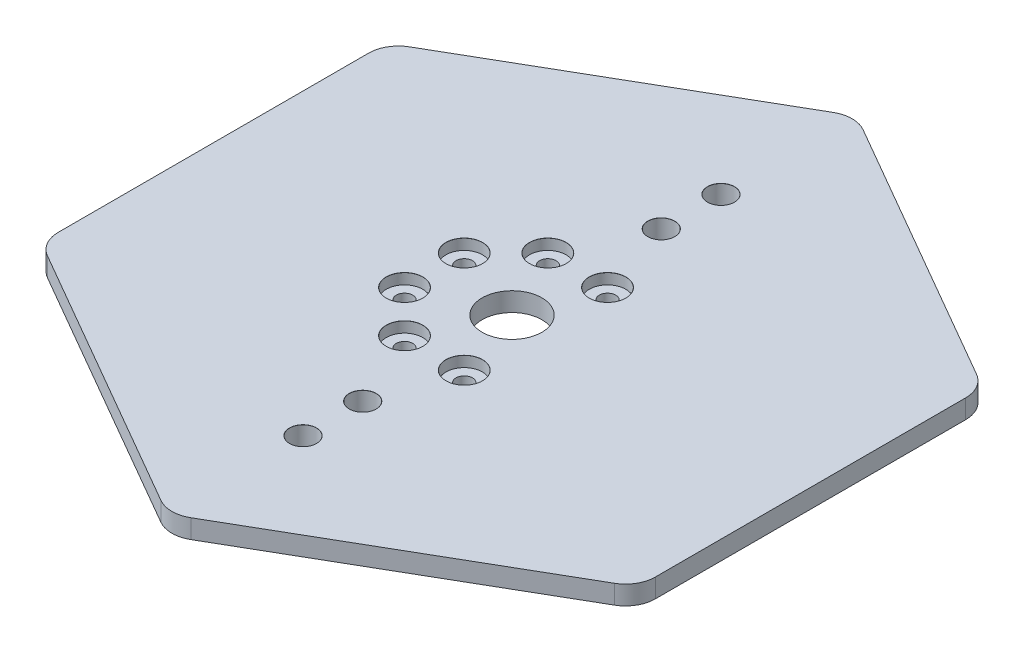
SolidWorks part; units mm, degrees
material "1060 Alloy"
ref_plane "Front Plane" through (0, 0, 0) normal (0, 0, 1) x (1, 0, 0)
ref_plane "Top Plane" through (0, 0, 0) normal (0, 1, 0) x (1, 0, 0)
ref_plane "Right Plane" through (0, 0, 0) normal (1, 0, 0) x (0, 0, -1)
sketch "Sketch1" plane through (0, 0, 0) normal (0, 1, 0) x (1, 0, 0)
  line L1 (100, 57.735) -> (0, 115.4701)
  line L2 (0, 115.4701) -> (-100, 57.735)
  line L3 (-100, 57.735) -> (-100, -57.735)
  line L4 (-100, -57.735) -> (0, -115.4701)
  line L5 (0, -115.4701) -> (100, -57.735)
  line L6 (100, -57.735) -> (100, 57.735)
  circle A0 centre (0, 0) radius 100 construction
  circle A1 centre (0, 0) radius 100 construction
  dimension "D1" = 200
extrude "Boss-Extrude1" add sketch "Sketch1" along normal blind 6.35
sketch "Sketch2" plane through (0, 6.35, 0) normal (0, 1, 0) x (1, 0, 0)
  circle A0 centre (0, 0) radius 10
  dimension "D1" = 20
extrude "Cut-Extrude1" cut sketch "Sketch2" against normal through all
sketch "Sketch3" plane through (0, 6.35, 0) normal (0, 1, 0) x (1, 0, 0)
  line L0 (0, -70) -> (0, 70) construction
  point P3 (0, 0)
  point P4 (0, -50)
  point P6 (0, 50)
  dimension "D1" = 140
  dimension "D2" = 20
  dimension "D3" = 20
hole_wizard "M8 Clearance Hole1" positions "Sketch4" profile "Sketch5" hole size "M8" standard "ANSI Metric" end condition through all
sketch "Sketch4" plane through (0, 6.35, 0) normal (0, 1, 0) x (1, 0, 0)
  point P0 (0, 70)
  point P3 (0, 50)
  point P6 (0, -50)
  point P9 (0, -70)
sketch "Sketch5" plane through (0, 6.35, -70) normal (1, 0, 0) x (0, 0, 1)
  line L0 (0, 0) -> (0, 6.35)
  line L1 (0, 6.35) -> (4.5, 6.35)
  line L2 (4.5, 6.35) -> (4.5, 0.025)
  line L3 (4.5, 0.025) -> (4.525, 0)
  line L5 (4.525, 0) -> (0, 0)
  line L6 (-4.5, 0.025) -> (-4.525, 0) construction
  line L11 (0, -6.35) -> (0, 107.95) construction
  dimension "Thru Hole Dia." = 9
  dimension "Thru Hole Depth" = 6.35
  dimension "Near C'Sink Dia." = 9.05
  dimension "Near C'Sink Angle" = 90
sketch "Sketch6" plane through (0, 6.35, 0) normal (0, 1, 0) x (1, 0, 0)
  line L0 (-55, 0) -> (55, 0) construction
  point P0 (-26, 10)
  point P1 (-12, 24)
  point P2 (8, 24)
  point P3 (8, 24)
  point P12 (8, -24)
  point P13 (-12, -24)
  point P14 (-26, -10)
  dimension "D1" = 8
  dimension "D2" = 24
  dimension "D3" = 26
  dimension "D4" = 20
  dimension "D5" = 10
hole_wizard "CBORE for M5 Hex Head Bolt1" positions "Sketch7" profile "Sketch8" counterbore size "M5" standard "ANSI Metric" end condition through all
sketch "Sketch7" plane through (0, 6.35, 0) normal (0, 1, 0) x (1, 0, 0)
  point P0 (-26, 10)
  point P3 (-12, 24)
  point P6 (8, 24)
  point P9 (-26, -10)
  point P12 (-12, -24)
  point P15 (8, -24)
sketch "Sketch8" plane through (-26, 6.35, -10) normal (1, 0, 0) x (0, 0, 1)
  line L0 (0, 0) -> (0, 6.35)
  line L1 (0, 6.35) -> (2.75, 6.35)
  line L3 (2.75, 6.35) -> (2.75, 3.58)
  line L4 (6.12, 3.58) -> (2.75, 3.58)
  line L5 (6.12, 3.58) -> (6.12, 0.025)
  line L6 (6.12, 0.025) -> (6.145, 0)
  line L7 (6.145, 0) -> (0, 0)
  line L8 (-6.12, 0.025) -> (-6.145, 0) construction
  line L11 (0, -6.35) -> (0, 107.95) construction
  dimension "Thru Hole Dia." = 5.5
  dimension "Thru Hole Depth" = 6.35
  dimension "C'Bore Dia." = 12.24
  dimension "C'Bore Depth" = 3.58
  dimension "Near C'Sink Dia." = 12.29
  dimension "Near C'Sink Angle" = 90
fillet "Fillet1" radius 10 6 edges at (0, 3.175, -115.4701) (-100, 3.175, -57.735) (-100, 3.175, 57.735) (100, 3.175, -57.735) (100, 3.175, 57.735) (0, 3.175, 115.4701)
